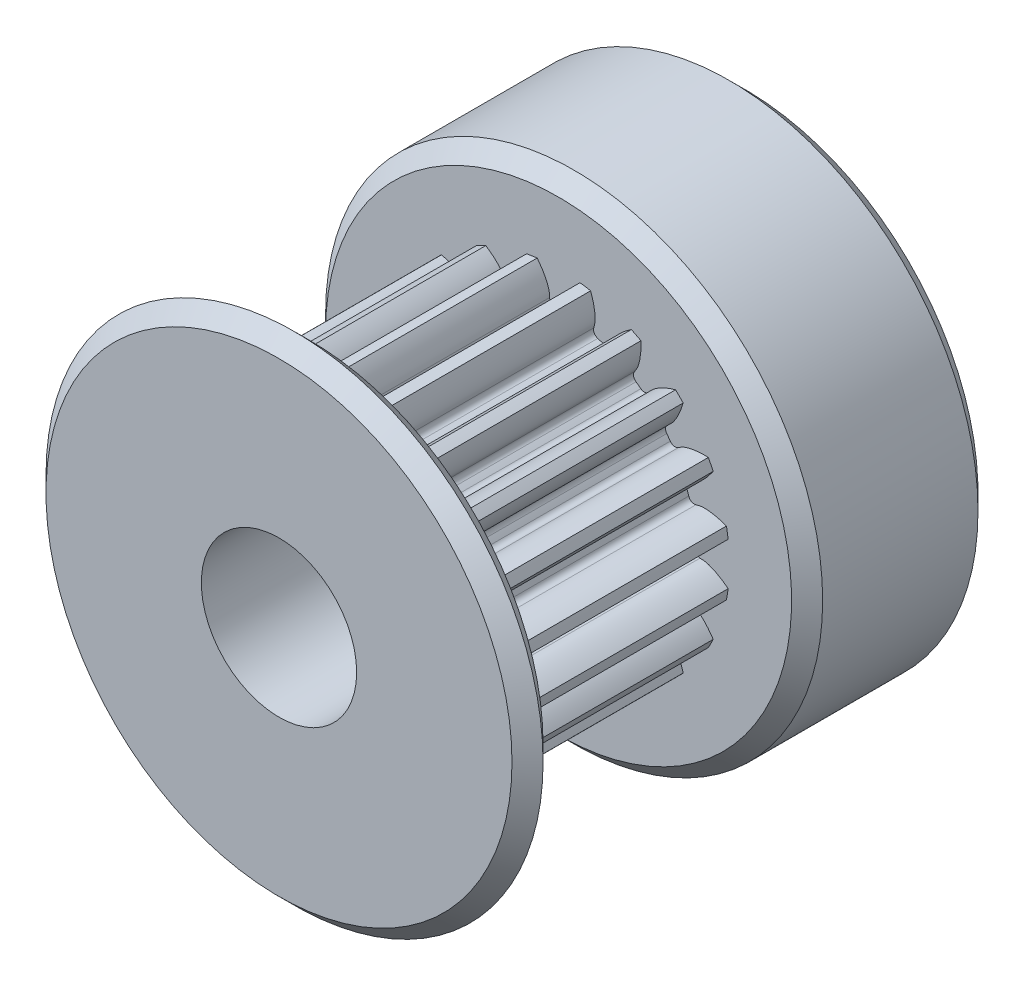
SolidWorks part; units mm, degrees
ref_plane "前视基准面" through (0, 0, 0) normal (0, 0, 1) x (1, 0, 0)
ref_plane "上视基准面" through (0, 0, 0) normal (0, 1, 0) x (1, 0, 0)
ref_plane "右视基准面" through (0, 0, 0) normal (1, 0, 0) x (0, 0, -1)
ref_axis "Axis1" through (0, 0, -88.99) along (0, 0, 1)
sketch "草图1" plane through (0, 0, 0) normal (0, 0, 1) x (1, 0, 0)
  circle A0 centre (0, 0) radius 5.5
extrude "LaShenA" add sketch "草图1" along normal blind 8
sketch "SketchA" plane through (0, 0, 8) normal (0, 0, 1) x (1, 0, 0)
  line L0 (0, 0) -> (0, 5.5) construction
  arc A0 (0.0963, 4.3739) -> (-0.0963, 4.3739) centre (0, 0) ccw
  arc A1 (0.8966, 5.6915) -> (-0.8966, 5.6915) centre (0, 0) ccw
  arc A2 (-0.0963, 4.3739) -> (-0.2902, 4.5522) centre (-0.1005, 4.5639) cw
  arc A3 (0.2902, 4.5522) -> (0.0963, 4.3739) centre (0.1005, 4.5639) cw
  circle A4 centre (0, 0) radius 4.6985 construction
  circle A5 centre (0, 0) radius 5.5 construction
  circle A6 centre (0, 0) radius 4.375 construction
  circle A7 centre (0, 0) radius 5 construction
  spline S0 degree 3 poles (0.2902, 4.5522) (0.293, 4.5981) (0.2941, 4.6581) (0.304, 4.7242) (0.3102, 4.7521) (0.3156, 4.7742) (0.3226, 4.7995) (0.3313, 4.828) (0.3419, 4.8596) (0.3546, 4.8941) (0.3694, 4.9315) (0.3867, 4.9717) (0.4065, 5.0147) (0.4291, 5.0602) (0.4545, 5.1081) (0.4829, 5.1584) (0.5145, 5.2109) (0.5494, 5.2655) (0.5878, 5.322) (0.6297, 5.3803) (0.6754, 5.4402) (0.7248, 5.5015) (0.7975, 5.5868) (0.8558, 5.6498) (0.8966, 5.6915) knots 0.125068 0.125068 0.125068 0.125068 0.215847 0.244833 0.257593 0.272674 0.290074 0.309794 0.331834 0.356194 0.382875 0.411875 0.443195 0.476835 0.512796 0.551076 0.591676 0.634597 0.679837 0.727398 0.777278 0.829478 0.883999 1 1 1 1
  spline S1 degree 3 poles (-0.2902, 4.5522) (-0.293, 4.5981) (-0.2941, 4.6581) (-0.304, 4.7242) (-0.3102, 4.7521) (-0.3156, 4.7742) (-0.3226, 4.7995) (-0.3313, 4.828) (-0.3419, 4.8596) (-0.3546, 4.8941) (-0.3694, 4.9315) (-0.3867, 4.9717) (-0.4065, 5.0147) (-0.4291, 5.0602) (-0.4545, 5.1081) (-0.4829, 5.1584) (-0.5145, 5.2109) (-0.5494, 5.2655) (-0.5878, 5.322) (-0.6297, 5.3803) (-0.6754, 5.4402) (-0.7248, 5.5015) (-0.7975, 5.5868) (-0.8558, 5.6498) (-0.8966, 5.6915) knots 0.125068 0.125068 0.125068 0.125068 0.215847 0.244833 0.257593 0.272674 0.290074 0.309794 0.331834 0.356194 0.382875 0.411875 0.443195 0.476835 0.512796 0.551076 0.591676 0.634597 0.679837 0.727398 0.777278 0.829478 0.883999 1 1 1 1
  dimension "D1" = 0.19
  dimension "Db" = 9.3969
  dimension "Da" = 11
  dimension "Df" = 8.75
  dimension "Dn" = 10
extrude "Cut-ExtrudeA" cut sketch "SketchA" against normal blind 8
pattern_circular "阵列(圆周)1" count 20 over 360 about axis through (0, 0, -88.99) along (0, 0, 1) of "Cut-ExtrudeA"
sketch "草图3" plane through (0, 0, 8) normal (0, 0, 1) x (1, 0, 0)
  circle A0 centre (0, 0) radius 8
  dimension "D1" = 16
extrude "凸台-拉伸2" add sketch "草图3" along normal blind 1
sketch "草图4" plane through (0, 0, 0) normal (0, 0, -1) x (-1, 0, 0)
  circle A0 centre (0, 0) radius 8
extrude "凸台-拉伸3" add sketch "草图4" along normal blind 6
chamfer "倒角1" distance 0.5 angle 45 4 edges at (-8, 0, -6) (-8, 0, 0) (8, 0, 8) (8, 0, 9)
sketch "草图5" plane through (0, 0, 9) normal (0, 0, 1) x (1, 0, 0)
  circle A0 centre (0, 0) radius 2.5
  dimension "D1" = 5
extrude "切除-拉伸2" cut sketch "草图5" against normal blind 16
